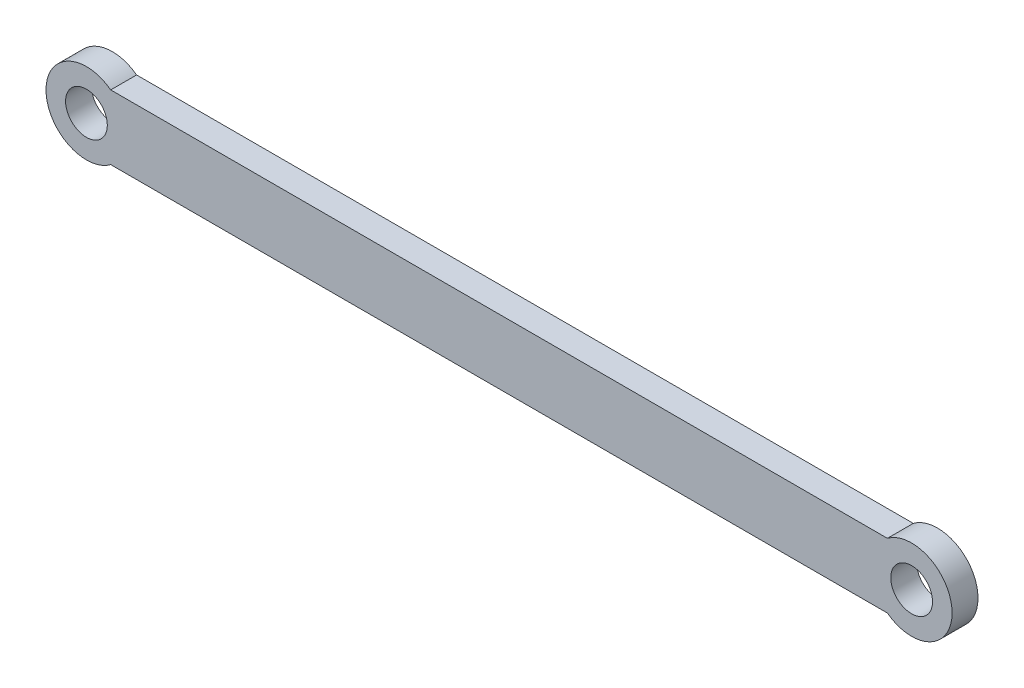
SolidWorks part; units mm, degrees
ref_plane "Front Plane" through (0, 0, 0) normal (0, 0, 1) x (1, 0, 0)
ref_plane "Top Plane" through (0, 0, 0) normal (0, 1, 0) x (1, 0, 0)
ref_plane "Right Plane" through (0, 0, 0) normal (1, 0, 0) x (0, 0, -1)
sketch "Sketch1" plane through (0, 0, 0) normal (0, 0, 1) x (1, 0, 0)
  line L1 (4.7625, 0) -> (157.1625, 0)
  line L3 (4.7625, 12.7) -> (157.1625, 12.7)
  arc A0 (4.7625, 12.7) -> (4.7625, 0) centre (0, 6.35) ccw
  arc A1 (157.1625, 0) -> (157.1625, 12.7) centre (161.925, 6.35) ccw
  dimension "D3" = 15.875
  dimension "D4" = 15.875
extrude "Boss-Extrude1" add sketch "Sketch1" along normal blind 5.08
sketch "Sketch2" plane through (0, 0, 0) normal (0, 0, -1) x (-1, 0, 0)
  circle A0 centre (-161.925, 6.35) radius 4.0958
  arc A1 (-157.1625, 12.7) -> (-157.1625, 0) centre (-161.925, 6.35) ccw construction
  circle A2 centre (0, 6.35) radius 4.0957
  arc A3 (-4.7625, 0) -> (-4.7625, 12.7) centre (0, 6.35) ccw construction
  dimension "D1" = 8.1915
  dimension "D2" = 8.1915
extrude "Cut-Extrude1" cut sketch "Sketch2" against normal up to surface (5.08 mm away) up to face at (80.9625, 6.35, 5.08)
